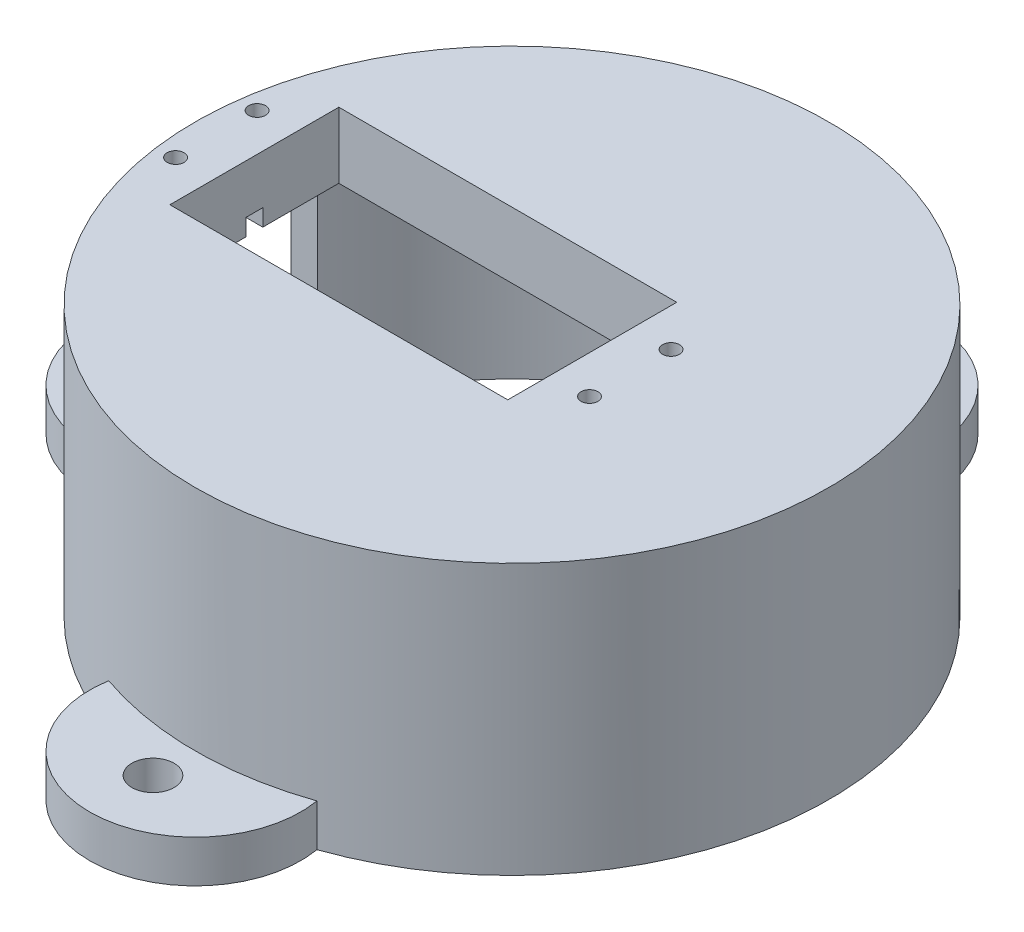
SolidWorks part; units mm, degrees
ref_plane "Front Plane" through (0, 0, 0) normal (0, 0, 1) x (1, 0, 0)
ref_plane "Top Plane" through (0, 0, 0) normal (0, 1, 0) x (1, 0, 0)
ref_plane "Right Plane" through (0, 0, 0) normal (1, 0, 0) x (0, 0, -1)
sketch "Sketch1" plane through (0, 0, 0) normal (0, 1, 0) x (1, 0, 0)
  arc A0 (-35.4167, -12.3252) -> (-12.3252, -35.4167) centre (0, 0) ccw
  arc A1 (12.3252, 35.4167) -> (-12.3252, 35.4167) centre (0, 37.5) ccw
  arc A2 (-35.4167, 12.3252) -> (-35.4167, -12.3252) centre (-37.5, 0) ccw
  arc A3 (-12.3252, -35.4167) -> (12.3252, -35.4167) centre (0, -37.5) ccw
  arc A4 (35.4167, -12.3252) -> (35.4167, 12.3252) centre (37.5, 0) ccw
  arc A5 (-12.3252, 35.4167) -> (-35.4167, 12.3252) centre (0, 0) ccw
  arc A6 (35.4167, 12.3252) -> (12.3252, 35.4167) centre (0, 0) ccw
  arc A7 (12.3252, -35.4167) -> (35.4167, -12.3252) centre (0, 0) ccw
  circle A8 centre (0, 0) radius 2.5
  circle A9 centre (-42.5, 0) radius 2.5
  circle A10 centre (0, 42.5) radius 2.5
  circle A11 centre (42.5, 0) radius 2.5
  circle A12 centre (0, -42.5) radius 2.5
  circle A13 centre (0, 0) radius 37.5
  dimension "D1" = 75
  dimension "D2" = 25
  dimension "D3" = 5
  dimension "D4" = 5
  dimension "D5" = 5
  dimension "D6" = 5
  dimension "D7" = 5
  dimension "D8" = 5
extrude "Boss-Extrude1" add sketch "Sketch1" along normal blind 32 contours A7 A13 A6 A5 A0 A8 region at (-36.4393, 0, 0)
extrude "Boss-Extrude2" add sketch "Sketch1<3>" along normal blind 5 contours A13 A2 A9 | A13 A3 A12 | A13 A1 A10 region at (-49.7106, 0, 0) region at (0, 0, 37.7894) region at (0, 0, -49.7106)
sketch "Sketch1<3>" plane through (0, 0, 0) normal (0, 1, 0) x (1, 0, 0) same geometry as "Sketch1"
sketch "Sketch2" plane through (0, 32, 0) normal (0, 1, 0) x (1, 0, 0)
  line L1 (-30.5, 10) -> (9.5, 10)
  line L2 (-30.5, 10) -> (-30.5, -10)
  line L3 (-30.5, -10) -> (9.5, -10)
  line L4 (9.5, 10) -> (9.5, -10)
  circle A0 centre (0, 0) radius 2.5
  circle A1 centre (-35, 4.825) radius 1
  circle A2 centre (-35, -4.825) radius 1
  circle A3 centre (14, 4.825) radius 1
  circle A4 centre (14, -4.825) radius 1
  dimension "D5" = 2
  dimension "D11" = 4.5
  dimension "D1" = 40
  dimension "D2" = 20
  dimension "D3" = 10
  dimension "D4" = 9.5
  dimension "D6" = 9.65
  dimension "D7" = 5.175
  dimension "D8" = 9.65
  dimension "D9" = 5.175
  dimension "D10" = 4.5
extrude "Cut-Extrude1" cut sketch "Sketch2" against normal up to surface (32 mm away) up to face at (0, 0, 2.5)
sketch "Sketch3" plane through (0, 0, 0) normal (0, -1, 0) x (-1, 0, 0)
  line L1 (33.0189, -10) -> (38.0189, -10)
  line L3 (33.0189, 10) -> (38.0189, 10)
  line L4 (38.0189, -10) -> (38.0189, 10)
  arc A0 (33.0189, 10) -> (33.0189, -10) centre (0, 0) ccw
  arc A1 (12.3252, -35.4167) -> (35.4167, -12.3252) centre (0, 0) ccw construction
  point P10 (0, 0)
  dimension "D1" = 3
  dimension "D2" = 5
extrude "Cut-Extrude2" cut sketch "Sketch3" against normal blind 24.2
sketch "Sketch4" plane through (0, 24.2, 0) normal (0, -1, 0) x (-1, 0, 0)
  line L0 (-9.5, -10) -> (-9.5, 10) construction
  line L1 (-9.5, -1) -> (-14.5, -1)
  line L2 (-9.5, -1) -> (-9.5, 1)
  line L3 (-9.5, 1) -> (-14.5, 1)
  line L4 (-14.5, -1) -> (-14.5, 1)
  line L5 (30.5, 10) -> (30.5, -10) construction
  line L6 (30.5, -1) -> (35.5, -1)
  line L7 (30.5, -1) -> (30.5, 1)
  line L8 (30.5, 1) -> (35.5, 1)
  line L9 (35.5, -1) -> (35.5, 1)
  circle A0 centre (-14, -4.825) radius 1 construction
  circle A1 centre (35, -4.825) radius 1 construction
  dimension "D3" = 3.825
  dimension "D1" = 2
  dimension "D2" = 2
  dimension "D4" = 3.825
  dimension "D5" = 5
  dimension "D6" = 5
extrude "Cut-Extrude3" cut sketch "Sketch4" against normal blind 2
